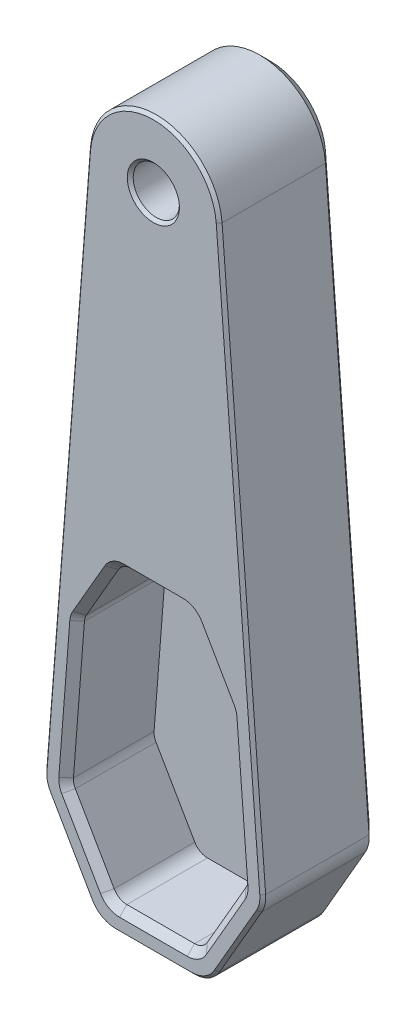
SolidWorks part; units mm, degrees
ref_plane "Front" through (0, 0, 0) normal (0, 0, 1) x (1, 0, 0)
ref_plane "Top" through (0, 0, 0) normal (0, 1, 0) x (1, 0, 0)
ref_plane "Right" through (0, 0, 0) normal (1, 0, 0) x (0, 0, -1)
sketch "Sketch1" plane through (0, 0, 0) normal (0, 0, 1) x (1, 0, 0)
  line L0 (-7.5056, -38.45) -> (-4.4864, 0.3491)
  line L3 (4.4864, 0.3491) -> (7.5056, -38.45)
  line L4 (0, 0) -> (0, -38.45) construction
  line L5 (185.5, -45.95) -> (0, -45.95) construction
  line L6 (0, -45.95) -> (0, -44.95) construction
  line L7 (-3.7528, -44.95) -> (3.7528, -44.95)
  line L8 (3.7528, -44.95) -> (7.5056, -38.45)
  line L9 (7.5056, -38.45) -> (3.7528, -31.95) construction
  line L10 (3.7528, -31.95) -> (-3.7528, -31.95) construction
  line L11 (-3.7528, -31.95) -> (-7.5056, -38.45) construction
  line L12 (-7.5056, -38.45) -> (-3.7528, -44.95)
  arc A2 (-4.4864, 0.3491) -> (4.4864, 0.3491) centre (0, 0) cw
  circle A4 centre (0, -38.45) radius 6.5 construction
  dimension "D1" = 4.5
  dimension "D2" = 13
  dimension "D3" = 1
extrude "Boss-Extrude2" add sketch "Sketch1" along normal blind 8
sketch "Sketch5" plane through (0, 0, 8) normal (0, 0, 1) x (1, 0, 0)
  line L9 (0, 0) -> (0, -38.45) construction
  line L10 (5.1831, -27.9387) -> (2.5915, -23.45)
  line L11 (2.5915, -23.45) -> (-2.5915, -23.45)
  line L12 (-2.5915, -23.45) -> (-5.1831, -27.9387)
  line L13 (-5.1831, -27.9387) -> (-2.5915, -32.4274) construction
  line L14 (-2.991, 0.2327) -> (-5.974, -38.1027)
  line L15 (-5.974, -38.1027) -> (-2.8868, -43.45)
  line L16 (-2.8868, -43.45) -> (2.8868, -43.45)
  line L17 (2.8868, -43.45) -> (5.974, -38.1027)
  line L18 (5.974, -38.1027) -> (2.991, 0.2327)
  line L19 (-2.991, 0.2327) -> (-5.974, -38.1027) construction
  line L20 (-5.974, -38.1027) -> (-2.8868, -43.45)
  line L21 (-2.8868, -43.45) -> (2.8868, -43.45)
  line L22 (2.8868, -43.45) -> (5.974, -38.1027)
  line L23 (5.974, -38.1027) -> (2.991, 0.2327) construction
  line L24 (-2.5915, -32.4274) -> (2.5915, -32.4274) construction
  line L25 (2.5915, -32.4274) -> (5.1831, -27.9387) construction
  line L26 (-5.1831, -27.9387) -> (-5.974, -38.1027)
  line L27 (5.1831, -27.9387) -> (5.974, -38.1027)
  circle A1 centre (0, -27.9387) radius 4.4887 construction
  arc A3 (2.991, 0.2327) -> (-2.991, 0.2327) centre (0, 0) ccw
  arc A4 (2.991, 0.2327) -> (-2.991, 0.2327) centre (0, 0) ccw construction
  dimension "D2" = 20
  dimension "D1" = 1.5
extrude "Rod Pocket" cut sketch "Sketch5" against normal offset from surface (6 mm away) 2 up to face at (0, -26.9918, 0)
fillet "Pocket Fillets" radius 1 8 edges at (-5.1831, -27.9387, 5) (-5.974, -38.1027, 5) (-2.8868, -43.45, 5) (2.8868, -43.45, 5) (5.974, -38.1027, 5) (5.1831, -27.9387, 5) (2.5915, -23.45, 5) (-2.5915, -23.45, 5)
sketch "Handle Profile Guide" plane through (0, 0, 0) normal (0, 0, 1) x (1, 0, 0)
  line L16 (-2.7503, -24.025) -> (-4.9398, -27.8173)
  line L17 (-5.0511, -28.1764) -> (-5.8004, -37.8053)
  line L18 (-5.6891, -38.2962) -> (-3.0455, -42.875)
  line L19 (-2.3094, -43.3) -> (2.3094, -43.3)
  line L20 (3.0455, -42.875) -> (5.6891, -38.2962)
  line L21 (5.8004, -37.8053) -> (5.0511, -28.1764)
  line L22 (4.9398, -27.8173) -> (2.7503, -24.025)
  line L23 (2.0142, -23.6) -> (-2.0142, -23.6)
  line L24 (-2.7503, -24.025) -> (-4.9398, -27.8173)
  line L25 (-5.0511, -28.1764) -> (-5.8004, -37.8053)
  line L26 (-5.6891, -38.2962) -> (-3.0455, -42.875)
  line L27 (-2.3094, -43.3) -> (2.3094, -43.3)
  line L28 (3.0455, -42.875) -> (5.6891, -38.2962)
  line L29 (5.8004, -37.8053) -> (5.0511, -28.1764)
  line L30 (4.9398, -27.8173) -> (2.7503, -24.025)
  line L31 (2.0142, -23.6) -> (-2.0142, -23.6)
  arc A16 (-2.0142, -23.6) -> (-2.7503, -24.025) centre (-2.0142, -24.45) ccw
  arc A17 (-4.9398, -27.8173) -> (-5.0511, -28.1764) centre (-4.2037, -28.2423) ccw
  arc A18 (-5.8004, -37.8053) -> (-5.6891, -38.2962) centre (-4.953, -37.8712) ccw
  arc A19 (-3.0455, -42.875) -> (-2.3094, -43.3) centre (-2.3094, -42.45) ccw
  arc A20 (2.3094, -43.3) -> (3.0455, -42.875) centre (2.3094, -42.45) ccw
  arc A21 (5.6891, -38.2962) -> (5.8004, -37.8053) centre (4.953, -37.8712) ccw
  arc A22 (5.0511, -28.1764) -> (4.9398, -27.8173) centre (4.2037, -28.2423) ccw
  arc A23 (2.7503, -24.025) -> (2.0142, -23.6) centre (2.0142, -24.45) ccw
  arc A24 (-2.0142, -23.6) -> (-2.7503, -24.025) centre (-2.0142, -24.45) ccw
  arc A25 (-4.9398, -27.8173) -> (-5.0511, -28.1764) centre (-4.2037, -28.2423) ccw
  arc A26 (-5.8004, -37.8053) -> (-5.6891, -38.2962) centre (-4.953, -37.8712) ccw
  arc A27 (-3.0455, -42.875) -> (-2.3094, -43.3) centre (-2.3094, -42.45) ccw
  arc A28 (2.3094, -43.3) -> (3.0455, -42.875) centre (2.3094, -42.45) ccw
  arc A29 (5.6891, -38.2962) -> (5.8004, -37.8053) centre (4.953, -37.8712) ccw
  arc A30 (5.0511, -28.1764) -> (4.9398, -27.8173) centre (4.2037, -28.2423) ccw
  arc A31 (2.7503, -24.025) -> (2.0142, -23.6) centre (2.0142, -24.45) ccw
  dimension "D1" = 0.15
fillet "Profile Fillets" radius 2 4 edges at (7.5056, -38.45, 4) (-7.5056, -38.45, 4) (3.7528, -44.95, 4) (-3.7528, -44.95, 4)
chamfer "Insert Cham" distance 0.5 angle 45 16 edges at (0, -43.45, 8) (2.8094, -43.316, 8) (-2.8094, -43.316, 8) (4.4972, -40.6606, 8) (-4.4972, -40.6606, 8) (5.9282, -38.0924, 8) (-5.9282, -38.0924, 8) (5.5753, -32.9792, 8) (-5.5753, -32.9792, 8) (5.1588, -27.9462, 8) (-5.1588, -27.9462, 8) (3.975, -25.8462, 8) (-3.975, -25.8462, 8) (2.5142, -23.584, 8) (-2.5142, -23.584, 8) (0, -23.45, 8)
sketch "Sketch6" plane through (0, 0, 0) normal (0, 0, -1) x (-1, 0, 0)
  circle A0 centre (0, 0) radius 2.875
  dimension "D1" = 5.75
extrude "Countersink" cut sketch "Sketch6" against normal blind 2.6
sketch "Sketch7" plane through (0, 0, 0) normal (0, 0, 1) x (1, 0, 0)
  circle A0 centre (0, 0) radius 1.575
  dimension "D1" = 3.15
extrude "Through Hole" cut sketch "Sketch7" along normal through all
chamfer "Deburs" distance 0.2 angle 45 13 edges at (1.575, 0, 8) (-1.575, 0, 2.6) (-2.875, 0, 0) (-7.414, -38.4292, 8) (-5.7628, -41.4685, 8) (-3.5981, -44.6821, 8) (0, -44.95, 8) (3.5981, -44.6821, 8) (5.7628, -41.4685, 8) (7.414, -38.4292, 8) (5.9719, -18.7414, 8) (0, 4.5, 8) (-5.9719, -18.7414, 8)
chamfer "Outside Chamfer" distance 0.75 angle 45 10 edges at (-5.9719, -18.7414, 0) (0, 4.5, 0) (-5.7628, -41.4685, 0) (0, -44.95, 0) (5.7628, -41.4685, 0) (5.9719, -18.7414, 0) (-3.5981, -44.6821, 0) (3.5981, -44.6821, 0) (-7.414, -38.4292, 0) (7.414, -38.4292, 0)
equation "\"D1@Sketch6\"=\"Hardware Head Countersink Diameter@Box Assy.Assembly\""
equation "\"D1@Sketch7\"=\"Hardware Clearance Hole Diameter@Box Assy.Assembly\""
equation "\"D1@Countersink\"=\"Nut Trap Depth@Box Assy.Assembly\""
